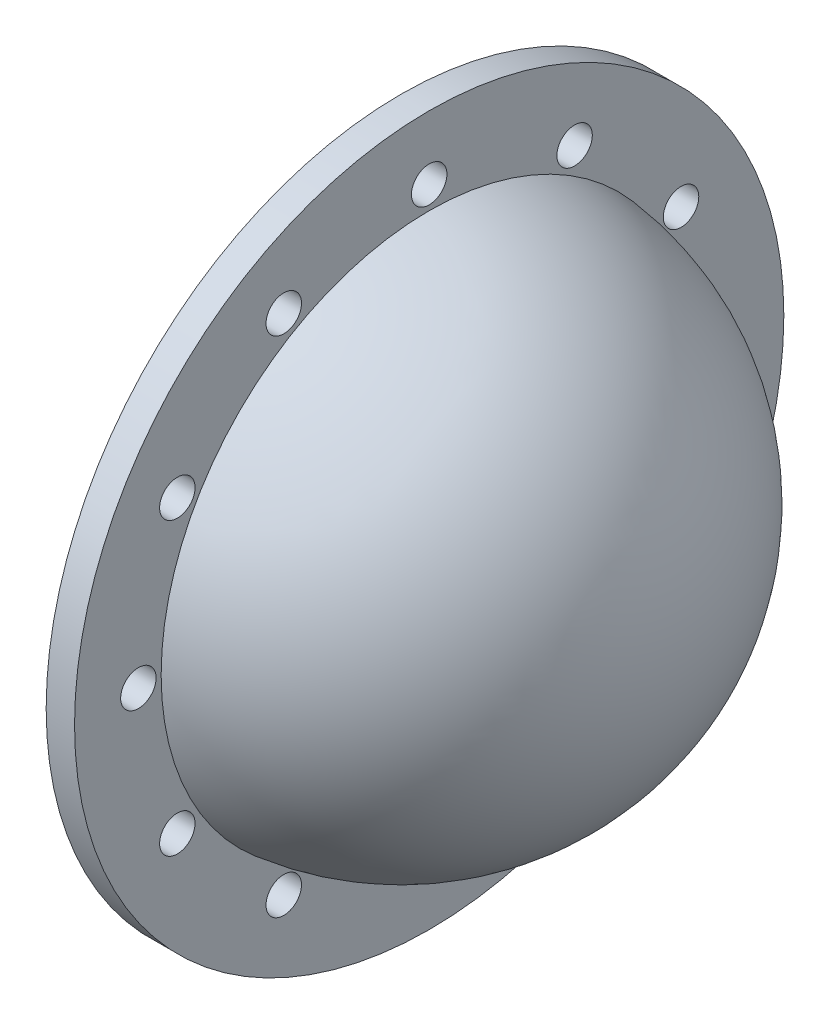
SolidWorks part; units mm, degrees
ref_plane "Front Plane" through (0, 0, 0) normal (0, 0, 1) x (1, 0, 0)
ref_plane "Top Plane" through (0, 0, 0) normal (0, 1, 0) x (1, 0, 0)
ref_plane "Right Plane" through (0, 0, 0) normal (1, 0, 0) x (0, 0, -1)
sketch "Sketch1" plane through (0, 0, 0) normal (1, 0, 0) x (0, 0, -1)
  circle A0 centre (0, 0) radius 2500
  circle A1 centre (0, 0) radius 2050 construction
  circle A2 centre (0, 2050) radius 125
  circle A3 centre (1025, 1775.3521) radius 125
  circle A4 centre (1775.3521, 1025) radius 125
  circle A5 centre (2050, 0) radius 125
  circle A6 centre (1775.3521, -1025) radius 125
  circle A7 centre (1025, -1775.3521) radius 125
  circle A8 centre (0, -2050) radius 125
  circle A9 centre (-1025, -1775.3521) radius 125
  circle A10 centre (-1775.3521, -1025) radius 125
  circle A11 centre (-2050, 0) radius 125
  circle A12 centre (-1775.3521, 1025) radius 125
  circle A13 centre (-1025, 1775.3521) radius 125
  point P30 (0, 0)
  dimension "D1" = 5000
  dimension "D2" = 4100
  dimension "D3" = 250
  dimension "D4" = 12
extrude "Boss-Extrude1" add sketch "Sketch1" along normal blind 200 contours A11 | A10 | A9 | A8 | A6 | A7 | A5 | A4 | A3 | A2 | A13 | A0 | A12 region at (0, 2050, 0) region at (0, 1775.3521, -1025) region at (0, 1025, -1775.3521) region at (0, 0, -2050) region at (0, -1025, -1775.3521) region at (0, -1775.3521, -1025) region at (0, -2050, 0) region at (0, -1775.3521, 1025) region at (0, -1025, 1775.3521) region at (0, 0, 2050) region at (0, 1775.3521, 1025)
sketch "Sketch2" plane through (0, 0, 0) normal (-1, 0, 0) x (0, 0, 1)
  circle A0 centre (0, 0) radius 1800
extrude "Cut-Extrude1" cut sketch "Sketch2" against normal through all
sketch "Sketch3" plane through (0, 0, 0) normal (-1, 0, 0) x (0, 0, 1)
  circle A0 centre (0, 0) radius 1800
  circle A2 centre (0, 0) radius 1900
ref_axis "Axis1" through (0, 0, 0) along (-1, 0, 0)
sketch "Sketch4" plane through (0, 0, 0) normal (-1, 0, 0) x (0, 0, 1)
  line L0 (0, 1900) -> (0, -1900) construction
  line L1 (0, 1800) -> (0, 1900)
  line L2 (0, -1900) -> (0, -1800)
  arc A0 (0, -1800) -> (0, 1800) centre (0, 0) ccw
  arc A1 (0, -1900) -> (0, 1900) centre (0, 0) ccw
revolve "Revolve1" add sketch "Sketch4" angle 180 about L2
